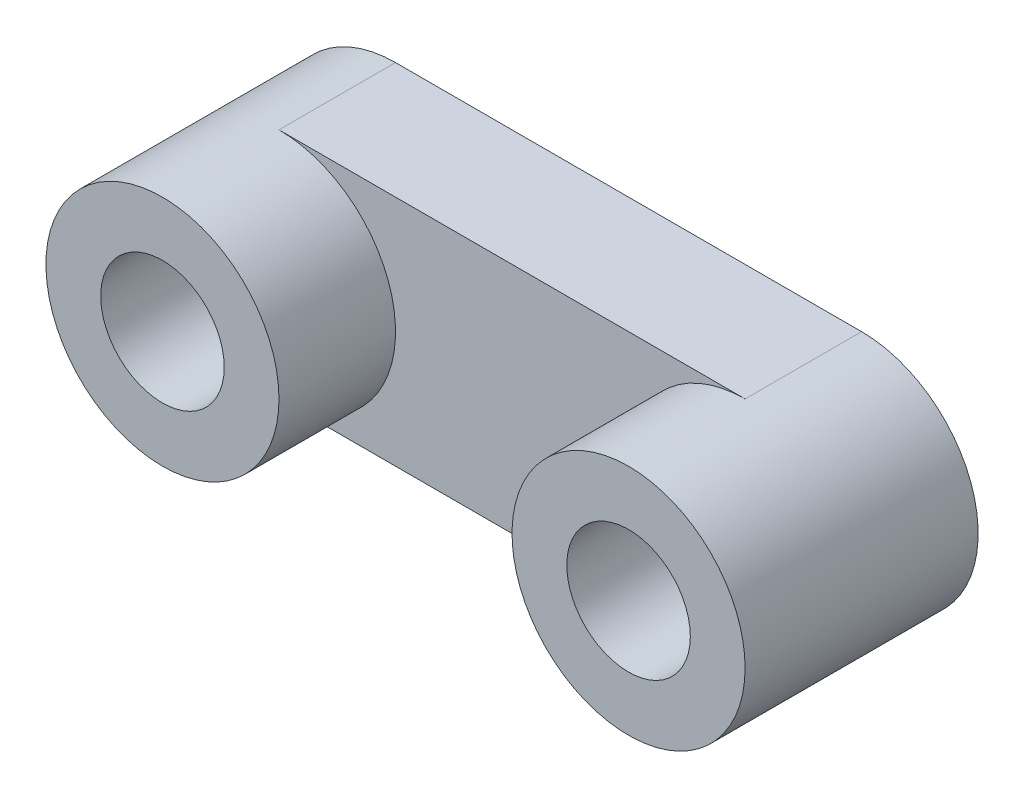
SolidWorks part; units mm, degrees
material "PET"
ref_plane "Piano frontale" through (0, 0, 0) normal (0, 0, 1) x (1, 0, 0)
ref_plane "Piano superiore" through (0, 0, 0) normal (0, 1, 0) x (1, 0, 0)
ref_plane "Piano destro" through (0, 0, 0) normal (1, 0, 0) x (0, 0, -1)
sketch "Schizzo1" plane through (0, 0, 0) normal (0, 0, 1) x (1, 0, 0)
  line L0 (-7.8622, 0) -> (12.1378, 0) construction
  line L1 (-7.8622, 5) -> (12.1378, 5)
  line L2 (-7.8622, -5) -> (12.1378, -5)
  arc A0 (-7.8622, 5) -> (-7.8622, -5) centre (-7.8622, 0) ccw
  arc A1 (12.1378, -5) -> (12.1378, 5) centre (12.1378, 0) ccw
  point P3 (2.1378, 0)
  dimension "D1" = 10
  dimension "D2" = 20
extrude "Estrusione-Estrusione1" add sketch "Schizzo1" along normal blind 5
sketch "Schizzo2" plane through (0, 0, 5) normal (0, 0, 1) x (1, 0, 0)
  line L0 (0, 0) -> (0, 8.3472) construction
  circle A0 centre (-7.8622, 0) radius 5
  arc A2 (-7.8622, 5) -> (-7.8622, -5) centre (-7.8622, 0) ccw construction
  circle A3 centre (-7.8622, 0) radius 2.65
  circle A4 centre (12.1378, 0) radius 5
  circle A5 centre (12.1378, 0) radius 2.65
  dimension "D1" = 10
  dimension "D3" = 10
  dimension "D5" = 5.3
  dimension "D2" = 0
  dimension "D4" = 20
extrude "Estrusione-Estrusione2" add sketch "Schizzo2" along normal blind 5
sketch "Schizzo3" plane through (0, 0, 5) normal (0, 0, 1) x (1, 0, 0)
  circle A0 centre (-7.8622, 0) radius 1.75
  circle A1 centre (12.1378, 0) radius 1.75
  dimension "D1" = 3.5
extrude "Taglio-Estrusione1" cut sketch "Schizzo3" against normal through all
ref_point "Punto2"
ref_point "Punto3"
ref_axis "Assi1" through (-7.8622, 0, 0) along (0, 0, 1)
ref_axis "Assi2" through (12.1378, 5, 5) along (-1, 0, 0)
